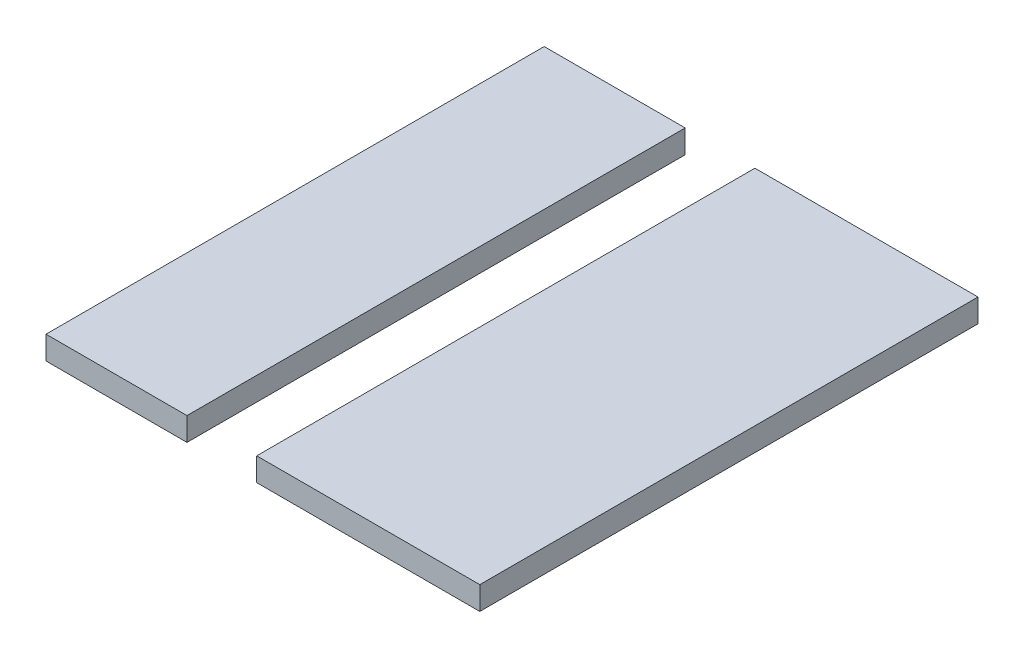
SolidWorks part; units mm, degrees
ref_plane "Front Plane" through (0, 0, 0) normal (0, 0, 1) x (1, 0, 0)
ref_plane "Top Plane" through (0, 0, 0) normal (0, 1, 0) x (1, 0, 0)
ref_plane "Right Plane" through (0, 0, 0) normal (1, 0, 0) x (0, 0, -1)
sketch "Sketch1" plane through (0, 0, 0) normal (0, 1, 0) x (1, 0, 0)
  line L0 (-0.8, -32.157) -> (-0.8, 32.157)
  line L1 (-28.7, -32.157) -> (28.7, -32.157) construction
  line L2 (-28.7, -32.157) -> (-28.7, 32.157) construction
  line L3 (-28.7, 32.157) -> (28.7, 32.157) construction
  line L4 (28.7, -32.157) -> (28.7, 32.157) construction
  line L5 (-9.8, 32.157) -> (-9.8, -32.157)
  line L6 (28, -32.157) -> (28, 32.157)
  line L7 (-28, -32.157) -> (-28, 32.157)
  line L8 (0, -32.157) -> (0, 32.157) construction
  line L9 (-0.8, -32.157) -> (28, -32.157)
  line L10 (28, 32.157) -> (-0.8, 32.157)
  line L11 (-9.8, 32.157) -> (-28, 32.157)
  line L12 (-9.8, -32.157) -> (-28, -32.157)
  line L13 (28.7, 0) -> (28, 0) construction
  line L14 (28, 20) -> (28.7, 20) construction
sketch "Sketch2" plane through (0, 0, 0) normal (0, 0, 1) x (1, 0, 0)
  line L0 (-0.8, 0) -> (28, 0) construction
  line L1 (28, 0) -> (-0.8, 0)
  line L2 (28, 0) -> (28, 3)
  line L3 (28, 3) -> (-0.8, 3)
  line L4 (-0.8, 0) -> (-0.8, 3)
  line L5 (28.7, 3) -> (-0.8, 3) construction
  line L7 (-9.8, 3) -> (-28, 3)
  line L8 (-9.8, 3) -> (-9.8, 0)
  line L9 (-9.8, 0) -> (-28, 0)
  line L10 (-28, 3) -> (-28, 0)
extrude "Boss-Extrude1" add sketch "Sketch1" along normal up to vertex (3 mm away) up to point (-28, 3, 0)
